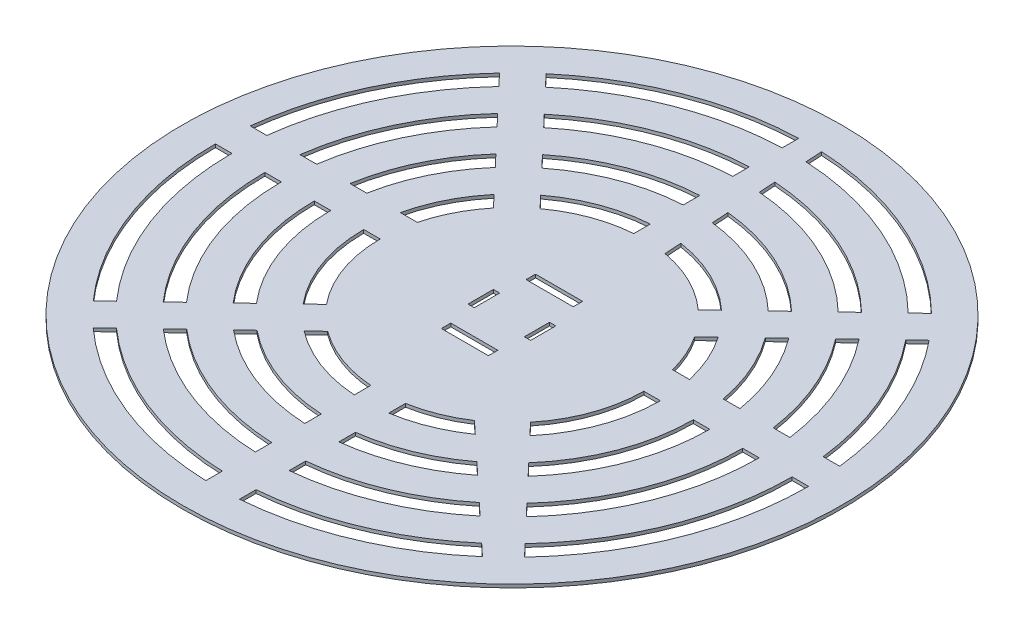
SolidWorks part; units mm, degrees
material "Oak"
ref_plane "Front Plane" through (0, 0, 0) normal (0, 0, 1) x (1, 0, 0)
ref_plane "Top Plane" through (0, 0, 0) normal (0, 1, 0) x (1, 0, 0)
ref_plane "Right Plane" through (0, 0, 0) normal (1, 0, 0) x (0, 0, -1)
sketch "Sketch1" plane through (0, 0, 0) normal (0, 1, 0) x (1, 0, 0)
  line L0 (-5.9097, -179.903) -> (-5.9097, -169.8972)
  line L1 (180, 0) -> (170, 0)
  line L2 (-134.5136, -119.6081) -> (-127.2587, -112.7175)
  line L3 (-116.5177, 137.1992) -> (-109.6197, 129.9366)
  line L4 (-131.0193, 123.4259) -> (-124.1213, 116.1632)
  line L5 (-120.4102, -133.7961) -> (-113.1357, -126.887)
  line L6 (14.0903, -179.4477) -> (14.0903, -169.4151)
  line L7 (178.8854, 20) -> (168.8194, 20)
  line L8 (-54.3454, 71.7397) -> (-47.4104, 64.438)
  line L9 (-144.984, 138.129) -> (130.4825, -151.9024) construction
  line L10 (61.912, -50.6647) -> (68.847, -57.9663)
  line L11 (-130.4825, 151.9024) -> (144.984, -138.129) construction
  line L12 (-5.9097, 79.7814) -> (-5.9097, 89.8058)
  line L13 (-5.9097, -222.8602) -> (-5.9097, 177.1398) construction
  line L15 (-165.6609, -149.1912) -> (124.3705, 126.2753) construction
  line L17 (14.0903, -222.8602) -> (14.0903, 177.1398) construction
  line L18 (66.803, 44.0155) -> (74.1558, 50.9991)
  line L19 (-151.8876, -163.6928) -> (138.1438, 111.7737) construction
  line L21 (200, 20) -> (-200, 20) construction
  line L22 (-80, 0) -> (-90, 0)
  line L23 (200, 0) -> (-200, 0) construction
  line L24 (-68.847, 57.9663) -> (-61.912, 50.6647)
  line L26 (44.0155, -66.803) -> (51.5086, -73.8029)
  line L27 (-77.4597, 20) -> (-87.7496, 20)
  line L28 (82.6904, -72.5417) -> (89.6033, -79.8201)
  line L31 (14.0903, 78.7494) -> (13.4777, 88.9851)
  line L32 (53.778, 59.2278) -> (61.0464, 66.1312)
  line L33 (66.3909, -87.7055) -> (73.7979, -94.6249)
  line L34 (14.0903, -88.8902) -> (14.0903, -78.7494)
  line L35 (-5.9097, -89.8058) -> (-5.9097, -79.7814)
  line L36 (-54.7489, -71.4322) -> (-47.396, -64.4486)
  line L37 (-69.1861, -57.5612) -> (-61.9176, -50.6577)
  line L38 (-108.1665, 20) -> (-118.3216, 20)
  line L39 (-110, 0) -> (-120, 0)
  line L40 (90, 0) -> (80, 0)
  line L41 (87.7496, 20) -> (77.4597, 20)
  line L42 (88.8051, 64.9127) -> (96.111, 71.8517)
  line L43 (75.5736, 79.9289) -> (82.834, 86.8247)
  line L44 (12.2612, 109.3145) -> (11.6557, 119.4326)
  line L45 (-5.9097, 109.8411) -> (-5.9097, 119.8544)
  line L46 (118.3216, 20) -> (108.1665, 20)
  line L47 (120, 0) -> (110, 0)
  line L48 (103.4178, -94.365) -> (110.3209, -101.6332)
  line L49 (88.5686, -108.4233) -> (95.9382, -115.3077)
  line L50 (14.0903, -119.1699) -> (14.0903, -109.0938)
  line L51 (-5.9097, -119.8544) -> (-5.9097, -109.8411)
  line L52 (-76.704, -92.2848) -> (-69.3981, -85.3458)
  line L53 (-90.9737, -78.2546) -> (-83.7133, -71.3589)
  line L54 (-140, 0) -> (-150, 0)
  line L55 (-138.5641, 20) -> (-148.6607, 20)
  line L56 (-89.6033, 79.8201) -> (-82.6904, 72.5417)
  line L57 (-75.1017, 93.5934) -> (-68.1888, 86.315)
  line L58 (-5.9097, 139.8752) -> (-5.9097, 149.8835)
  line L59 (10.4483, 139.6096) -> (9.8458, 149.6765)
  line L60 (97.3507, 100.6124) -> (104.6075, 107.5048)
  line L61 (110.699, 85.7072) -> (117.9844, 92.6266)
  line L62 (119.119, 121.2875) -> (126.3739, 128.1781)
  line L63 (132.5427, 106.4539) -> (139.8171, 113.363)
  line L64 (148.6607, 20) -> (138.5641, 20)
  line L65 (150, 0) -> (140, 0)
  line L66 (124.1213, -116.1632) -> (131.0193, -123.4259)
  line L67 (110.6552, -129.0559) -> (118.0051, -135.922)
  line L68 (14.0903, -149.3367) -> (14.0903, -139.2891)
  line L69 (-5.9097, -149.8835) -> (-5.9097, -139.8752)
  line L70 (-98.5774, -113.0597) -> (-91.2921, -106.1403)
  line L71 (-112.7472, -98.9347) -> (-105.4903, -92.0423)
  line L72 (-170, 0) -> (-180, 0)
  line L73 (-168.8194, 20) -> (-178.8854, 20)
  line L74 (-110.3209, 101.6332) -> (-103.4178, 94.365)
  line L75 (-95.8193, 115.4065) -> (-88.9162, 108.1384)
  line L76 (-5.9097, 169.8972) -> (-5.9097, 179.903)
  line L77 (8.6428, 169.7802) -> (8.042, 179.8203)
  circle A0 centre (0, 0) radius 200
  arc A1 (-80, 0) -> (-61.9176, -50.6577) centre (0, 0) ccw
  arc A2 (-110, 0) -> (-83.7133, -71.3589) centre (0, 0) ccw
  arc A3 (-140, 0) -> (-105.4903, -92.0423) centre (0, 0) ccw
  arc A4 (-170, 0) -> (-127.2587, -112.7175) centre (0, 0) ccw
  arc A5 (-180, 0) -> (-134.5136, -119.6081) centre (0, 0) ccw
  arc A6 (-150, 0) -> (-112.7472, -98.9347) centre (0, 0) ccw
  arc A7 (-120, 0) -> (-90.9737, -78.2546) centre (0, 0) ccw
  arc A8 (-90, 0) -> (-69.1861, -57.5612) centre (0, 0) ccw
  circle A9 centre (0, 0) radius 180 construction
  circle A10 centre (0, 0) radius 170 construction
  circle A11 centre (0, 0) radius 150 construction
  circle A12 centre (0, 0) radius 140 construction
  circle A13 centre (0, 0) radius 120 construction
  circle A14 centre (0, 0) radius 110 construction
  circle A15 centre (0, 0) radius 90 construction
  circle A16 centre (0, 0) radius 80 construction
  arc A17 (77.4597, 20) -> (66.803, 44.0155) centre (0, 0) ccw
  arc A18 (87.7496, 20) -> (74.1558, 50.9991) centre (0, 0) ccw
  arc A19 (108.1665, 20) -> (88.8051, 64.9127) centre (0, 0) ccw
  arc A20 (118.3216, 20) -> (96.111, 71.8517) centre (0, 0) ccw
  arc A21 (138.5641, 20) -> (110.699, 85.7072) centre (0, 0) ccw
  arc A22 (148.6607, 20) -> (117.9844, 92.6266) centre (0, 0) ccw
  arc A23 (168.8194, 20) -> (132.5427, 106.4539) centre (0, 0) ccw
  arc A24 (178.8854, 20) -> (139.8171, 113.363) centre (0, 0) ccw
  arc A25 (126.3739, 128.1781) -> (8.042, 179.8203) centre (0, 0) ccw
  arc A26 (119.119, 121.2875) -> (8.6428, 169.7802) centre (0, 0) ccw
  arc A27 (104.6075, 107.5048) -> (9.8458, 149.6765) centre (0, 0) ccw
  arc A28 (97.3507, 100.6124) -> (10.4483, 139.6096) centre (0, 0) ccw
  arc A29 (82.834, 86.8247) -> (11.6557, 119.4326) centre (0, 0) ccw
  arc A30 (75.5736, 79.9289) -> (12.2612, 109.3145) centre (0, 0) ccw
  arc A31 (61.0464, 66.1312) -> (13.4777, 88.9851) centre (0, 0) ccw
  arc A32 (53.778, 59.2278) -> (14.0903, 78.7494) centre (0, 0) ccw
  arc A33 (14.0903, -78.7494) -> (44.0155, -66.803) centre (0, 0) ccw
  arc A34 (14.0903, -88.8902) -> (51.5086, -73.8029) centre (0, 0) ccw
  arc A35 (61.912, -50.6647) -> (80, 0) centre (0, 0) ccw
  arc A36 (68.847, -57.9663) -> (90, 0) centre (0, 0) ccw
  arc A37 (82.6904, -72.5417) -> (110, 0) centre (0, 0) ccw
  arc A38 (89.6033, -79.8201) -> (120, 0) centre (0, 0) ccw
  arc A39 (103.4178, -94.365) -> (140, 0) centre (0, 0) ccw
  arc A40 (110.3209, -101.6332) -> (150, 0) centre (0, 0) ccw
  arc A41 (124.1213, -116.1632) -> (170, 0) centre (0, 0) ccw
  arc A42 (131.0193, -123.4259) -> (180, 0) centre (0, 0) ccw
  arc A43 (14.0903, -179.4477) -> (118.0051, -135.922) centre (0, 0) ccw
  arc A44 (14.0903, -169.4151) -> (110.6552, -129.0559) centre (0, 0) ccw
  arc A45 (14.0903, -149.3367) -> (95.9382, -115.3077) centre (0, 0) ccw
  arc A46 (14.0903, -139.2891) -> (88.5686, -108.4233) centre (0, 0) ccw
  arc A47 (14.0903, -119.1699) -> (73.7979, -94.6249) centre (0, 0) ccw
  arc A48 (14.0903, -109.0938) -> (66.3909, -87.7055) centre (0, 0) ccw
  arc A49 (-120.4102, -133.7961) -> (-5.9097, -179.903) centre (0, 0) ccw
  arc A50 (-113.1357, -126.887) -> (-5.9097, -169.8972) centre (0, 0) ccw
  arc A51 (-98.5774, -113.0597) -> (-5.9097, -149.8835) centre (0, 0) ccw
  arc A52 (-91.2921, -106.1403) -> (-5.9097, -139.8752) centre (0, 0) ccw
  arc A53 (-76.704, -92.2848) -> (-5.9097, -119.8544) centre (0, 0) ccw
  arc A54 (-69.3981, -85.3458) -> (-5.9097, -109.8411) centre (0, 0) ccw
  arc A55 (-54.7489, -71.4322) -> (-5.9097, -89.8058) centre (0, 0) ccw
  arc A56 (-47.396, -64.4486) -> (-5.9097, -79.7814) centre (0, 0) ccw
  arc A57 (-131.0193, 123.4259) -> (-178.8854, 20) centre (0, 0) ccw
  arc A58 (-124.1213, 116.1632) -> (-168.8194, 20) centre (0, 0) ccw
  arc A59 (-110.3209, 101.6332) -> (-148.6607, 20) centre (0, 0) ccw
  arc A60 (-103.4178, 94.365) -> (-138.5641, 20) centre (0, 0) ccw
  arc A61 (-89.6033, 79.8201) -> (-118.3216, 20) centre (0, 0) ccw
  arc A62 (-82.6904, 72.5417) -> (-108.1665, 20) centre (0, 0) ccw
  arc A63 (-68.847, 57.9663) -> (-87.7496, 20) centre (0, 0) ccw
  arc A64 (-61.912, 50.6647) -> (-77.4597, 20) centre (0, 0) ccw
  arc A65 (-5.9097, 79.7814) -> (-47.4104, 64.438) centre (0, 0) ccw
  arc A66 (-5.9097, 89.8058) -> (-54.3454, 71.7397) centre (0, 0) ccw
  arc A67 (-5.9097, 109.8411) -> (-68.1888, 86.315) centre (0, 0) ccw
  arc A68 (-5.9097, 119.8544) -> (-75.1017, 93.5934) centre (0, 0) ccw
  arc A69 (-5.9097, 139.8752) -> (-88.9162, 108.1384) centre (0, 0) ccw
  arc A70 (-5.9097, 149.8835) -> (-95.8193, 115.4065) centre (0, 0) ccw
  arc A71 (-5.9097, 169.8972) -> (-109.6197, 129.9366) centre (0, 0) ccw
  arc A72 (-5.9097, 179.903) -> (-116.5177, 137.1992) centre (0, 0) ccw
  arc A74 (-123.8091, -130.6572) -> (-5.9097, -179.903) centre (0, 0) ccw
  arc A75 (-180, 0) -> (-134.5136, -119.6081) centre (0, 0) ccw
  arc A76 (-131.0193, 123.4259) -> (-178.8854, 20) centre (0, 0) ccw
  arc A77 (-5.9097, 179.903) -> (-116.5177, 137.1992) centre (0, 0) ccw
  arc A78 (126.3739, 128.1781) -> (8.042, 179.8203) centre (0, 0) ccw
  arc A79 (178.8854, 20) -> (139.8171, 113.363) centre (0, 0) ccw
  arc A80 (131.0193, -123.4259) -> (180, 0) centre (0, 0) ccw
  arc A81 (14.0903, -179.4477) -> (118.0051, -135.922) centre (0, 0) ccw
  point P18 (0, 0)
  point P22 (0, 0)
  point P26 (0, 0)
  dimension "D1" = 400
  dimension "D2" = 10
  dimension "D6" = 20
  dimension "D7" = 20
  dimension "D8" = 20
  dimension "D9" = 20
  dimension "D4" = 20
  dimension "D5" = 20
  dimension "D3" = 20
extrude "Boss-Extrude1" add sketch "Sketch1" along normal blind 2 contours A0 A72 L76 A71 L3 A70 L58 A69 L75 A68 L45 A67 L57 A66 L12 A65 L8 A42 L66 A41 L1 A40 L48 A39 L65 A38 L28 A37 L47 A36 L10 A35 L40 A34 L34 A33 L26 A24 L7 region at (0.1124, 0, 0.0959)
scale "Scale1" scale about centroid uniform scaling yes scale factor 0.525
sketch "Sketch2" plane through (0, 1.525, 0) normal (0, 1, 0) x (1, 0, 0)
  line L5 (-7.5, 12) -> (7.5, 12)
  line L24 (-7.5, -15) -> (7.5, -15)
  line L25 (-7.5, -15) -> (-7.5, -12)
  line L26 (-7.5, 15) -> (7.5, 15)
  line L27 (7.5, -15) -> (7.5, -12)
  line L30 (-7.5, -12) -> (7.5, -12)
  line L31 (7.5, 12) -> (7.5, 15)
  line L34 (-7.5, 12) -> (-7.5, 15)
  point P0 (0, 0)
  point P1 (0, 0)
  point P4 (0, -15)
  point P6 (0, 0)
  dimension "D1" = 15
  dimension "D2" = 30
  dimension "D3" = 3
  dimension "D4" = 3
extrude "Cut-Extrude2" cut sketch "Sketch2" against normal blind 10 contours L5 L31 L26 L34 | L24 L27 L30 L25
sketch "Sketch3" plane through (0, 1.525, 0) normal (0, 1, 0) x (1, 0, 0)
  line L0 (-10, -4.0035) -> (-10, 4.0807)
  line L2 (-8, -4.0035) -> (-8, 4.0807)
  line L4 (7.9887, -4.053) -> (8.0111, 3.9433)
  line L5 (-10, -4.0035) -> (-8, -4.0035)
  line L6 (7.9887, -4.053) -> (9.9887, -4.053)
  line L10 (8.0111, 3.9433) -> (10.0111, 3.9433)
  line L11 (10.0111, 3.9433) -> (9.9887, -4.053)
  line L12 (5.9946, -4) -> (-6, -4) construction
  line L14 (-8, 4.0807) -> (-10, 4.0807)
  line L15 (5.9946, 4) -> (-6, 4) construction
  point P0 (0, 0)
  dimension "D1" = 8
  dimension "D2" = 4
  dimension "D3" = 4
  dimension "D6" = 8
extrude "Cut-Extrude5" cut sketch "Sketch3" against normal blind 10 contours L2 L14 L0 L5 | L10 L4 L6 region at (-9, 1.525, -0.0386) region at (8.9999, 1.525, 0.0548)
